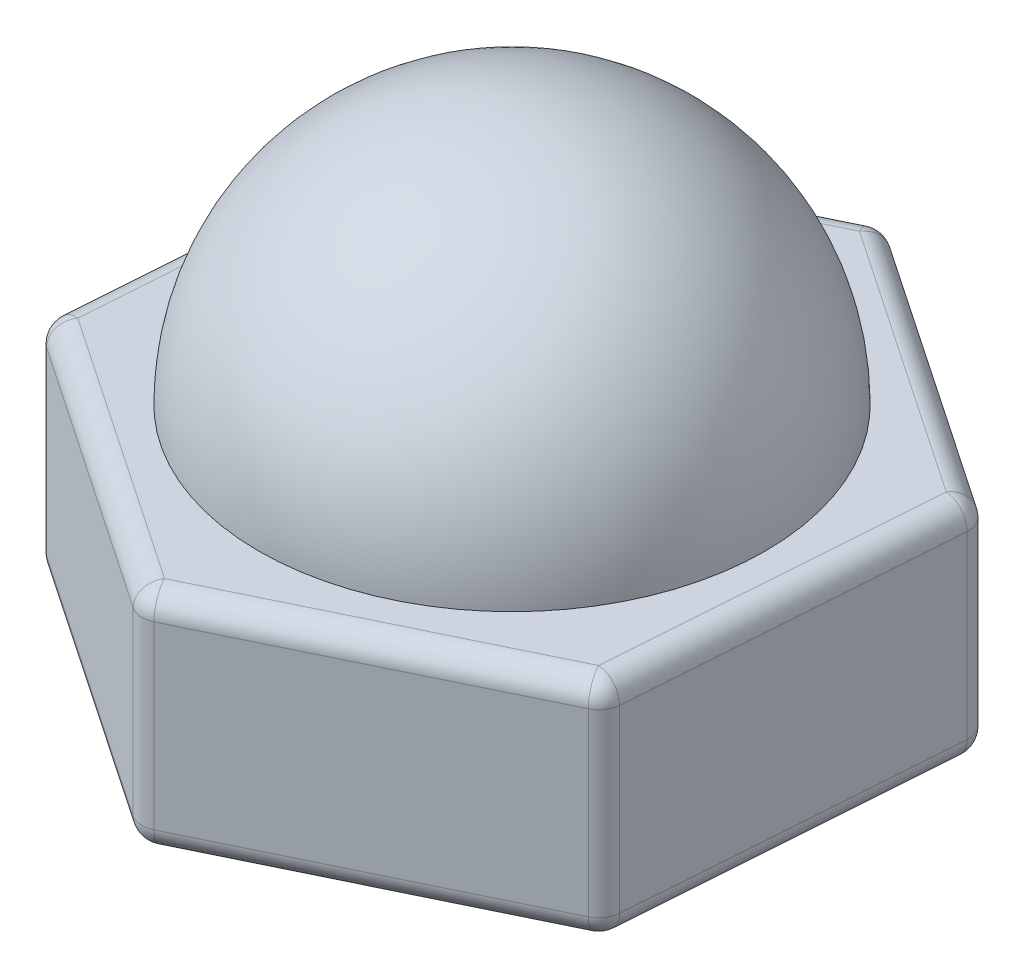
SolidWorks part; units mm, degrees
ref_plane "Front Plane" through (0, 0, 0) normal (0, 0, 1) x (1, 0, 0)
ref_plane "Top Plane" through (0, 0, 0) normal (0, 1, 0) x (1, 0, 0)
ref_plane "Right Plane" through (0, 0, 0) normal (1, 0, 0) x (0, 0, -1)
sketch "Hexagonal Base Sketch" plane through (0, 0, 0) normal (0, 1, 0) x (1, 0, 0)
  line L1 (-2.5809, 1.749) -> (-2.8051, -1.3606)
  line L2 (-2.8051, -1.3606) -> (-0.2243, -3.1096)
  line L3 (-0.2243, -3.1096) -> (2.5809, -1.749)
  line L4 (2.5809, -1.749) -> (2.8051, 1.3606)
  line L5 (2.8051, 1.3606) -> (0.2243, 3.1096)
  line L6 (0.2243, 3.1096) -> (-2.5809, 1.749)
  circle A0 centre (0, 0) radius 2.7 construction
  dimension "D1" = 5.4
extrude "Hexagonal Base" add sketch "Hexagonal Base Sketch" along normal blind 2
sketch "Hemisphere Sketch" plane through (0, 0, 0) normal (0, 0, 1) x (1, 0, 0)
  line L0 (-0.2243, 2) -> (2.5809, 2) construction
  line L1 (0, 2) -> (0, 4.25)
  line L2 (0, 2) -> (2.25, 2)
  arc A0 (2.25, 2) -> (0, 4.25) centre (0, 2) ccw
revolve "Hemisphere" add sketch "Hemisphere Sketch" angle 360 about L1
sketch "Outer Thread Circle" plane through (0, 0, 0) normal (0, -1, 0) x (1, 0, 0)
  circle A0 centre (0, 0) radius 1.25
fillet "Base Fillet" radius 0.2 18 edges at (-2.693, 0, -0.1942) (-1.5147, 0, 2.2351) (1.1783, 0, 2.4293) (2.693, 0, 0.1942) (1.5147, 0, -2.2351) (-1.1783, 0, -2.4293) (2.5809, 1, 1.749) (-0.2243, 1, 3.1096) (-2.8051, 1, 1.3606) (-2.5809, 1, -1.749) (0.2243, 1, -3.1096) (2.8051, 1, -1.3606) (-1.5147, 2, 2.2351) (-2.693, 2, -0.1942) (-1.1783, 2, -2.4293) (1.5147, 2, -2.2351) (2.693, 2, 0.1942) (1.1783, 2, 2.4293)
extrude "Outer Thread Surface" cut sketch "Outer Thread Circle" against normal blind 3.7
ref_plane "Thread Plane" through (0, 3.585, 0) normal (0, -1, 0) x (-1, 0, 0)
sketch "Main Thread Circle" plane through (0, 3.585, 0) normal (0, -1, 0) x (-1, 0, 0)
  circle A0 centre (0, 0) radius 1.25 construction
  circle A1 centre (0, 0) radius 1.25
curve "Thread Helix/Spiral" pitch 0.48 height 4.77 radius 1.25 centre (0, 3.585, 0) axis (0, -1, 0) start towards (0, 0, 1)
sketch "Thread Sweep Cut Profile" plane through (0, 0, 0) normal (1, 0, 0) x (0, 0, -1)
  line L0 (-1.2191, 3.6821) -> (-1.4191, 3.618)
  line L1 (-1.4191, 3.618) -> (-1.4191, 3.518)
  line L2 (-1.4191, 3.518) -> (-1.2191, 3.454)
  line L3 (-1.2191, 3.454) -> (-1.2191, 3.6821)
  spline S0 degree 3 poles (-1.25, 3.585) (-1.25, 3.5751) (-1.1849, 3.555) (-0.9069, 3.525) (-0.3521, 3.485) (0.3521, 3.445) (0.9069, 3.405) (1.1849, 3.375) (1.2825, 3.345) (1.1849, 3.315) (0.9069, 3.285) (0.3521, 3.245) (-0.3521, 3.205) (-0.9069, 3.165) (-1.1849, 3.135) (-1.2825, 3.105) (-1.1849, 3.075) (-0.9069, 3.045) (-0.3521, 3.005) (0.3521, 2.965) (0.9069, 2.925) (1.1849, 2.895) (1.2825, 2.865) (1.1849, 2.835) (0.9069, 2.805) (0.3521, 2.765) (-0.3521, 2.725) (-0.9069, 2.685) (-1.1849, 2.655) (-1.2825, 2.625) (-1.1849, 2.595) (-0.9069, 2.565) (-0.3521, 2.525) (0.3521, 2.485) (0.9069, 2.445) (1.1849, 2.415) (1.2825, 2.385) (1.1849, 2.355) (0.9069, 2.325) (0.3521, 2.285) (-0.3521, 2.245) (-0.9069, 2.205) (-1.1849, 2.175) (-1.2825, 2.145) (-1.1849, 2.115) (-0.9069, 2.085) (-0.3521, 2.045) (0.3521, 2.005) (0.9069, 1.965) (1.1849, 1.935) (1.2825, 1.905) (1.1849, 1.875) (0.9069, 1.845) (0.3521, 1.805) (-0.3521, 1.765) (-0.9069, 1.725) (-1.1849, 1.695) (-1.2825, 1.665) (-1.1849, 1.635) (-0.9069, 1.605) (-0.3521, 1.565) (0.3521, 1.525) (0.9069, 1.485) (1.1849, 1.455) (1.2825, 1.425) (1.1849, 1.395) (0.9069, 1.365) (0.3521, 1.325) (-0.3521, 1.285) (-0.9069, 1.245) (-1.1849, 1.215) (-1.2825, 1.185) (-1.1849, 1.155) (-0.9069, 1.125) (-0.3521, 1.085) (0.3521, 1.045) (0.9069, 1.005) (1.1849, 0.975) (1.2825, 0.945) (1.1849, 0.915) (0.9069, 0.885) (0.3521, 0.845) (-0.3521, 0.805) (-0.9069, 0.765) (-1.1849, 0.735) (-1.2825, 0.705) (-1.1849, 0.675) (-0.9069, 0.645) (-0.3521, 0.605) (0.3521, 0.565) (0.9069, 0.525) (1.1849, 0.495) (1.2825, 0.465) (1.1849, 0.435) (0.9069, 0.405) (0.3521, 0.365) (-0.3521, 0.325) (-0.9069, 0.285) (-1.1849, 0.255) (-1.2825, 0.225) (-1.1849, 0.195) (-0.9069, 0.165) (-0.3521, 0.125) (0.3521, 0.085) (0.9069, 0.045) (1.1849, 0.015) (1.2825, -0.015) (1.1849, -0.045) (0.9069, -0.075) (0.3521, -0.115) (-0.3521, -0.155) (-0.9069, -0.195) (-1.1849, -0.225) (-1.2825, -0.255) (-1.1849, -0.285) (-0.9069, -0.315) (-0.3521, -0.355) (0.3521, -0.395) (0.9069, -0.435) (1.1849, -0.465) (1.2825, -0.495) (1.1849, -0.525) (0.9069, -0.555) (0.3521, -0.595) (-0.3521, -0.635) (-0.9069, -0.675) (-1.1849, -0.705) (-1.2825, -0.735) (-1.1849, -0.765) (-0.9069, -0.795) (-0.3521, -0.835) (0.3521, -0.875) (0.9069, -0.915) (1.1849, -0.945) (1.2825, -0.975) (1.1849, -1.005) (0.9069, -1.035) (0.4908, -1.065) (0, -1.095) (-0.4909, -1.125) (-0.9067, -1.155) (-1.0926, -1.1751) (-1.1548, -1.185) knots 0 0 0 0 0.006289 0.012579 0.018868 0.031447 0.037736 0.044025 0.050314 0.056604 0.062893 0.069182 0.081761 0.08805 0.09434 0.100629 0.106918 0.113208 0.119497 0.132075 0.138365 0.144654 0.150943 0.157233 0.163522 0.169811 0.18239 0.188679 0.194969 0.201258 0.207547 0.213836 0.220126 0.232704 0.238994 0.245283 0.251572 0.257862 0.264151 0.27044 0.283019 0.289308 0.295597 0.301887 0.308176 0.314465 0.320755 0.333333 0.339623 0.345912 0.352201 0.358491 0.36478 0.371069 0.383648 0.389937 0.396226 0.402516 0.408805 0.415094 0.421384 0.433962 0.440252 0.446541 0.45283 0.459119 0.465409 0.471698 0.484277 0.490566 0.496855 0.503145 0.509434 0.515723 0.522013 0.534591 0.540881 0.54717 0.553459 0.559748 0.566038 0.572327 0.584906 0.591195 0.597484 0.603774 0.610063 0.616352 0.622642 0.63522 0.641509 0.647799 0.654088 0.660377 0.666667 0.672956 0.685535 0.691824 0.698113 0.704403 0.710692 0.716981 0.72327 0.735849 0.742138 0.748428 0.754717 0.761006 0.767296 0.773585 0.786164 0.792453 0.798742 0.805031 0.811321 0.81761 0.823899 0.836478 0.842767 0.849057 0.855346 0.861635 0.867925 0.874214 0.886792 0.893082 0.899371 0.90566 0.91195 0.918239 0.924528 0.937107 0.943396 0.949686 0.955975 0.962264 0.968553 0.974843 0.981132 0.987421 0.993711 1 1 1 1 construction
  point P4 (-1.2191, 3.568)
  dimension "D1" = 0.2281
  dimension "D2" = 0.1
  dimension "D3" = 0.21
sweep "Thread Sweep Cut" cut profiles "Thread Sweep Cut Profile" path "Thread Helix/Spiral" align with end faces yes
